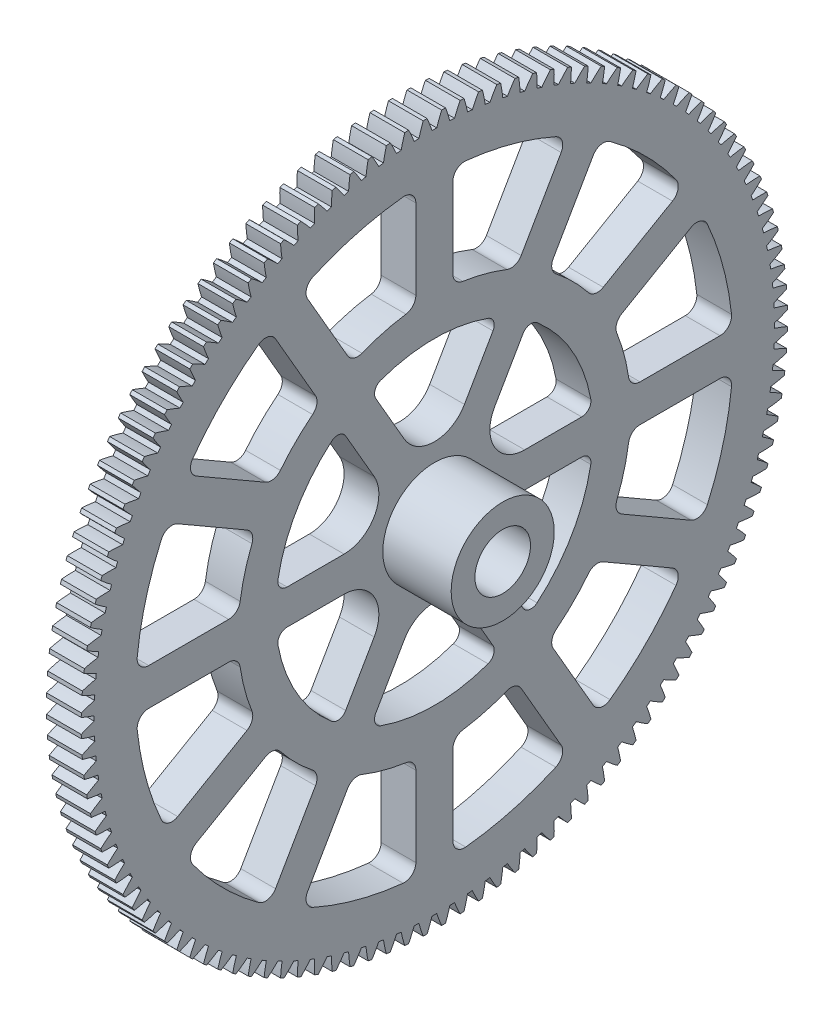
SolidWorks part; units mm, degrees
ref_plane "Plane1" through (0, 0, 0) normal (0, 0, 1) x (1, 0, 0)
ref_plane "Plane2" through (0, 0, 0) normal (0, 1, 0) x (1, 0, 0)
ref_plane "Plane3" through (0, 0, 0) normal (1, 0, 0) x (0, 0, -1)
sketch "HoldingSke" plane through (0, 0, 0) normal (0, 1, 0) x (1, 0, 0)
  line L0 (0, 0) -> (-1, -1.7321)
  line L1 (-15, 0) -> (100, 0) construction
  line L2 (0, 0) -> (-2.1039, 2.3779)
  line L3 (0, 0) -> (-11.863, 4.5341)
  line L4 (0, 0) -> (-4.318, 7.479)
  line L5 (0, 0) -> (-46.8476, -17.4728)
  line L6 (0, 0) -> (-2.4869, -1.6779)
  line L7 (-2.1039, 2.3779) -> (8.6586, 51.2059)
  line L8 (-76.2, 54.61) -> (-74.8, 54.61)
  line L9 (-71.009, 38.7566) -> (-53.1078, 45.2721)
  line L10 (-76.2, 71.12) -> (104.1128, 71.12)
  line L11 (0, 0) -> (-3, 0)
  line L12 (-76.2, 101.6) -> (-76.181, 101.6)
  line L13 (24.9733, 27.94) -> (52.9518, 28.4284)
  line L14 (24.9733, 27.94) -> (24.9743, 27.94)
  line L15 (24.9733, 27.94) -> (100.4006, 29.5858)
  line L16 (-63.627, -0.5) -> (-12.827, -0.5)
  circle A0 centre (0, 0) radius 4
  circle A1 centre (0, 0) radius 29.374
  circle A2 centre (0, 0) radius 37.5
  circle A3 centre (0, 0) radius 4
  dimension "Num_teeth" = 120
  dimension "Pitch_radius" = 180.3128
  dimension "Width" = 3
  dimension "Thickness" = 3
sketch "BasProSke" plane through (0, 0, 0) normal (0, 1, 0) x (1, 0, 0)
  line L0 (-10, 0) -> (60, 0) construction
  line L1 (0, 0) -> (0, 30.5)
  line L2 (0, 0) -> (3, 0)
  line L3 (3, 0) -> (3, 30.5)
  line L4 (3, 30.5) -> (0, 30.5)
  dimension "Thickness" = 3
  dimension "Diameter" = 61
revolve "Base-Revolve" add sketch "BasProSke" angle 360 about L0
sketch "TooCutSke" plane through (0, 0, 0) normal (1, 0, 0) x (0, 0, -1)
  line L1 (0, 0) -> (0, 107) construction
  line L2 (0, 0) -> (-0.4259, 29.997) construction
  line L3 (0, 0) -> (-1.5705, 59.9751) construction
  line L4 (-0.4259, 29.997) -> (-0.7853, 29.9876) construction
  arc A0 (0.2052, 29.3733) -> (-0.2052, 29.3733) centre (0, 0) ccw
  arc A1 (0.6411, 30.5187) -> (-0.6411, 30.5187) centre (0, 0) ccw
  circle A2 centre (0, 0) radius 30 construction
  circle A3 centre (0, 0) radius 28.1908 construction
  arc A4 (-0.2052, 29.3733) -> (-0.6411, 30.5187) centre (-11.6236, 25.6829) ccw
  arc A5 (0.6411, 30.5187) -> (0.2052, 29.3733) centre (11.6236, 25.6829) ccw
extrude "ToothCut" cut sketch "TooCutSke" along normal through all
fillet "Breaks" [suppressed] radius 0.01 tangent propagation no
fillet "RootFillets" [suppressed] radius 0.126
pattern_circular "TeethCuts" count 120 every 3 about axis through (-10, 0, 0) along (1, 0, 0) of "ToothCut", "RootFillets", "Breaks"
sketch "HubNeaOneSke" plane through (0, 0, 0) normal (-1, 0, 0) x (0, 0, 1)
  circle A0 centre (0, 0) radius 29.374
  dimension "Diameter" = 58.748
extrude "HubNearOne" [suppressed] add sketch "HubNeaOneSke" along normal blind 47.0001
sketch "HubNeaBotSke" plane through (0, 0, 0) normal (-1, 0, 0) x (0, 0, 1)
  circle A0 centre (0, 0) radius 29.374
  dimension "Diameter" = 58.748
extrude "HubNearBoth" [suppressed] add sketch "HubNeaBotSke" along normal blind 23.5
ref_plane "FarPln" through (3, 0, 0) normal (1, 0, 0) x (0, 0, -1)
sketch "HubFarSke" plane through (3, 0, 0) normal (1, 0, 0) x (0, 0, -1)
  circle A0 centre (0, 0) radius 29.374
  dimension "Diameter" = 58.748
extrude "HubFar" [suppressed] add sketch "HubFarSke" along normal blind 23.5
sketch "BorSke" plane through (0, 0, 0) normal (1, 0, 0) x (0, 0, -1)
  circle A0 centre (0, 0) radius 2.4
  dimension "Diameter" = 4.8
extrude "Bore" cut sketch "BorSke" along normal mid plane 100.0001
sketch "KeySke" plane through (0, 0, 0) normal (1, 0, 0) x (0, 0, -1)
  line L0 (-1.5, 0) -> (-1.5, 5.4)
  line L1 (-1.5, 5.4) -> (1.5, 5.4)
  line L2 (1.5, 5.4) -> (1.5, 0)
  line L3 (0, 0) -> (0, 34) construction
  line L4 (-1.5, 0) -> (1.5, 0)
  dimension "Width" = 3
extrude "Keyway" [suppressed] cut sketch "KeySke" along normal mid plane 100.0001
pattern_circular "Keyway2" [suppressed] count 2 every 90 about axis through (-10, 0, 0) along (1, 0, 0) reverse direction yes
sketch "Esquisse1" plane through (3, 0, 0) normal (1, 0, 0) x (0, 0, -1)
  circle A0 centre (0, 0) radius 2.4
  circle A1 centre (0, 0) radius 4.45
  circle A2 centre (0, 0) radius 2.4 construction
  dimension "D1" = 8.9
extrude "Boss.-Extru.1" add sketch "Esquisse1" along normal blind 5.9
sketch "Esquisse2" plane through (0, 0, 0) normal (-1, 0, 0) x (0, 0, 1)
  line L0 (-6.8625, 11.8862) -> (0, 0) construction
  line L1 (6.8625, 11.8862) -> (0, 0) construction
  line L2 (0, 13.725) -> (0, 0) construction
  line L3 (-5.5224, 12.565) -> (-2.5981, 7.5)
  line L4 (5.5224, 12.565) -> (2.5981, 7.5)
  arc A0 (-6.8625, 11.8862) -> (6.8625, 11.8862) centre (0, 0) cw construction
  arc A1 (-5.5224, 12.565) -> (5.5224, 12.565) centre (0, 0) cw
  arc A2 (-2.5981, 7.5) -> (2.5981, 7.5) centre (0, 9) ccw
  point P11 (0, 6)
  dimension "D1" = 13.725
  dimension "D2" = 60
  dimension "D3" = 1.5
  dimension "D4" = 6
extrude "Enlèv. mat.-Extru.1" cut sketch "Esquisse2" against normal through all
fillet "Congé1" radius 0.8 2 edges at (1.5, 12.565, 5.5224) (1.5, 12.565, -5.5224)
pattern_circular "Répétition circulaire1" count 6 over 360 about axis through (8.9, 0, 0) along (-1, 0, 0) of "Enlèv. mat.-Extru.1", "Congé1"
sketch "Esquisse4" plane through (3, 0, 0) normal (1, 0, 0) x (0, 0, -1)
  line L0 (0, 0) -> (-13.2322, 22.9189) construction
  line L1 (0, 0) -> (0, 26.7267) construction
  line L2 (-1.6, 16.8743) -> (-1.6, 25.7503)
  line L3 (-7.0515, 15.4136) -> (-11.4895, 23.1004)
  arc A0 (-8.475, 14.6791) -> (0, 16.95) centre (0, 0) cw construction
  arc A1 (-12.9, 22.3435) -> (0, 25.8) centre (0, 0) cw construction
  arc A2 (-11.4895, 23.1004) -> (-1.6, 25.7503) centre (0, 0) cw
  arc A3 (-7.0515, 15.4136) -> (-1.6, 16.8743) centre (0, 0) cw
  dimension "D3" = 25.8
  dimension "D1" = 16.95
  dimension "D2" = 30
  dimension "D4" = 3.2
  dimension "D5" = 3.2
extrude "Enlèv. mat.-Extru.2" cut sketch "Esquisse4" against normal through all
fillet "Congé2" radius 1 4 edges at (1.5, 25.7503, 1.6) (1.5, 23.1004, 11.4895) (1.5, 16.8743, 1.6) (1.5, 15.4136, 7.0515)
pattern_circular "Répétition circulaire2" count 12 over 360 about axis through (8.9, 0, 0) along (-1, 0, 0) of "Congé2", "Enlèv. mat.-Extru.2"
equation "' \"Module@HoldingSke\" = 6.35"
equation "' \"Num_teeth@HoldingSke\" = 12"
equation "' \"Ap@HoldingSke\" =  20"
equation "' \"Ap@HoldingSke\" = 20"
equation "' \"Width@HoldingSke\" = 0.5 * 25.4"
equation "' \"Hub_dia@HoldingSke\"= 1 * 25.4"
equation "' \"Hub_dia@HoldingSke\" = 1 * 25.4"
equation "' \"Overall_len@HoldingSke\" = 1.0 * 25.4"
equation "' \"Bore@HoldingSke\" = 0.75 * 25.4"
equation "' \"T_dim@HoldingSke\" = 0.1 * 25.4"
equation "' \"Width@KeySke\" = 0.25 * 25.4"
equation "' \"Show_teeth@HoldingSke\" = 13"
equation "' \"Backlash@HoldingSke\" = 0.009 * 25.4"
equation "' \"Addendum_fac@HoldingSke\" = 1.0"
equation "' \"Dedendum_fac@HoldingSke\" = 1.25"
equation "' \"Dedendum_add@HoldingSke\" = 0.00005 * 25.4"
equation "' \"Clearance_fac@HoldingSke\" = 0.25"
equation "\"Pitch@HoldingSke\" = 1 / \"Module@HoldingSke\""
equation "\"Overcut_dia@TooCutSke\" = (\"Num_teeth@HoldingSke\" + 2 * \"Addendum_fac@HoldingSke\") / \"Pitch@HoldingSke\" + 0.002 * 25.4"
equation "\"Pitch_dia@TooCutSke\" = \"Num_teeth@HoldingSke\" / \"Pitch@HoldingSke\""
equation "\"Base_dia@TooCutSke\" = \"Num_teeth@HoldingSke\" / \"Pitch@HoldingSke\" * cos((\"Ap@HoldingSke\"  * 3.14159265 / 180))"
equation "\"Root_dia@TooCutSke\" = (\"Num_teeth@HoldingSke\" + 2) / \"Pitch@HoldingSke\" - 2 * (\"Addendum_fac@HoldingSke\" + \"Dedendum_fac@HoldingSke\") / \"Pitch@HoldingSke\" - \"Dedendum_add@HoldingSke\" * 2"
equation "\"Half_ang@TooCutSke\" = 180 / \"Num_teeth@HoldingSke\""
equation "\"Half_CT@TooCutSke\" = \"Num_teeth@HoldingSke\" / \"Pitch@HoldingSke\" * sin((3.14159265 / 2 / \"Num_teeth@HoldingSke\")) / 2 - 7 * \"Backlash@HoldingSke\" / 4"
equation "\"Flank_rad@TooCutSke\" = \"Num_teeth@HoldingSke\" / \"Pitch@HoldingSke\" / 5"
equation "\"Radius@RootFillets\" = \"Clearance_fac@HoldingSke\" / \"Pitch@HoldingSke\" + \"Dedendum_add@HoldingSke\""
equation "\"Break_rad@Breaks\" = 0.02 / \"Pitch@HoldingSke\""
equation "\"Thickness@HoldingSke\" = \"Width@HoldingSke\""
equation "\"OAL@HoldingSke\" = \"Thickness@HoldingSke\""
equation "\"MHD@HoldingSke\" = (\"Num_teeth@HoldingSke\" + 2) / \"Pitch@HoldingSke\" - 2 * (\"Addendum_fac@HoldingSke\" + \"Dedendum_fac@HoldingSke\")  / \"Pitch@HoldingSke\" - \"Dedendum_add@HoldingSke\" * 2"
equation "\"MBD@HoldingSke\" = (\"Num_teeth@HoldingSke\" + 2) / \"Pitch@HoldingSke\" - 2 * (\"Addendum_fac@HoldingSke\" + \"Dedendum_fac@HoldingSke\")  / \"Pitch@HoldingSke\" - \"Dedendum_add@HoldingSke\" * 2 - 0.002 * 25.4"
equation "\"MHD@HoldingSke\" = ((sgn( \"MHD@HoldingSke\" - \"Hub_dia@HoldingSke\" )-1)*( \"MHD@HoldingSke\" - \"Hub_dia@HoldingSke\" ))/-2+ \"Hub_dia@HoldingSke\""
equation "\"MBD@HoldingSke\" = ((sgn( \"MBD@HoldingSke\" - \"Bore@HoldingSke\" )-1)*( \"MBD@HoldingSke\" - \"Bore@HoldingSke\" ))/-2+ \"Bore@HoldingSke\""
equation "\"OAL@HoldingSke\" = ((sgn( \"OAL@HoldingSke\" - \"Overall_len@HoldingSke\" )+1)*( \"OAL@HoldingSke\" - \"Overall_len@HoldingSke\" ))/2 + \"Overall_len@HoldingSke\" + 0.000002 * 25.4"
equation "\"Num_teeth@TeethCuts\" = int( \"Show_teeth@HoldingSke\" ) + 1"
equation "\"Num_teeth@TeethCuts\" = ((sgn( \"Num_teeth@TeethCuts\" - \"Num_teeth@HoldingSke\" )-1)*( \"Num_teeth@TeethCuts\" - \"Num_teeth@HoldingSke\" ))/-2+ \"Num_teeth@HoldingSke\""
equation "\"Num_teeth@TeethCuts\" = ((sgn( \"Num_teeth@TeethCuts\" - 2.0)+1)*( \"Num_teeth@TeethCuts\" - 2.0))/2 +2.0"
equation "\"Angle@TeethCuts\" = 360.0 / \"Num_teeth@HoldingSke\""
equation "\"Diameter@BasProSke\" = (\"Num_teeth@HoldingSke\" + 2 * \"Addendum_fac@HoldingSke\") / \"Pitch@HoldingSke\""
equation "\"Thickness@BasProSke\"  = \"Thickness@HoldingSke\""
equation "' \"Fillet_rad@BasProSke\" =  \"Thickness@HoldingSke\" * 0.05"
equation "' \"Fillet_rad@BasProSke\" = \"Thickness@HoldingSke\" * 0.05"
equation "\"MHD@HoldingSke\" = ((sgn( \"MHD@HoldingSke\" - \"Root_dia@TooCutSke\" )-1)*( \"MHD@HoldingSke\" - \"Root_dia@TooCutSke\" ))/-2+ \"Root_dia@TooCutSke\""
equation "\"Diameter@HubNeaOneSke\" = \"MHD@HoldingSke\""
equation "\"Length@HubNearOne\" = \"OAL@HoldingSke\" - \"Thickness@BasProSke\""
equation "\"Diameter@HubNeaBotSke\" = \"MHD@HoldingSke\""
equation "\"Length@HubNearBoth\" = ( \"OAL@HoldingSke\" - \"Thickness@BasProSke\" ) / 2.0"
equation "\"Thickness@FarPln\" = \"Thickness@BasProSke\""
equation "\"Diameter@HubFarSke\" = \"MHD@HoldingSke\""
equation "\"Length@HubFar\" = ( \"OAL@HoldingSke\" - \"Thickness@BasProSke\" ) / 2.0"
equation "\"D1@Bore\" = \"OAL@HoldingSke\" * 2.0"
equation "\"D1@Keyway\" = \"OAL@HoldingSke\" * 2.0"
equation "\"Offset@KeySke\" = \"T_dim@HoldingSke\" + \"MBD@HoldingSke\" / 2.0"
